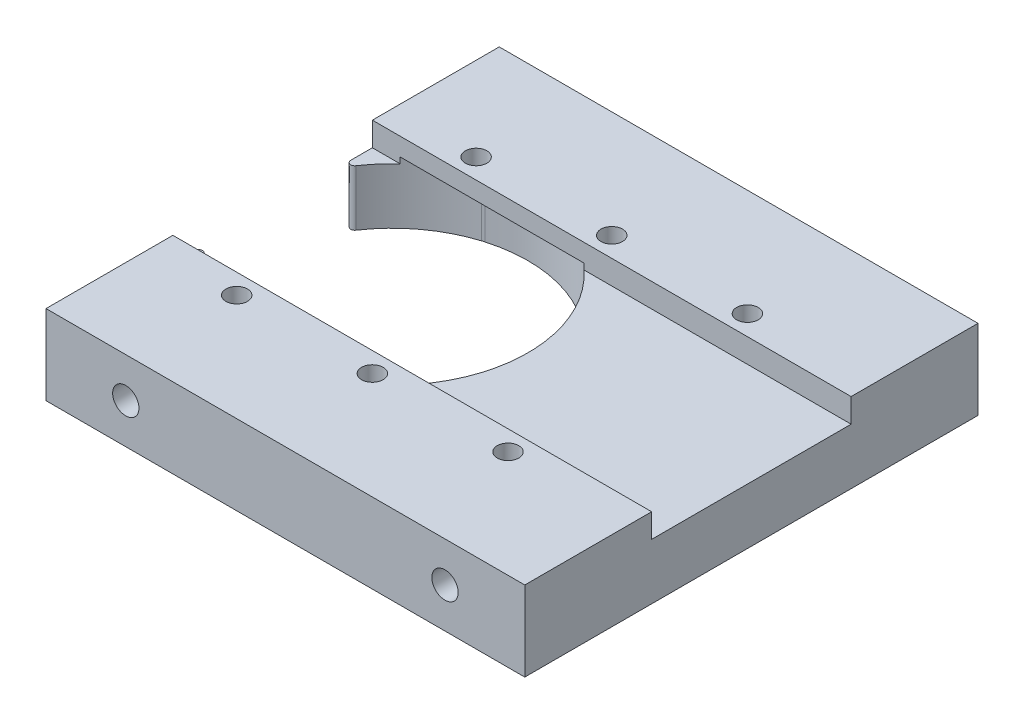
SolidWorks part; units mm, degrees
ref_plane "前视基准面" through (0, 0, 0) normal (0, 0, 1) x (1, 0, 0)
ref_plane "上视基准面" through (0, 0, 0) normal (0, 1, 0) x (1, 0, 0)
ref_plane "右视基准面" through (0, 0, 0) normal (1, 0, 0) x (0, 0, -1)
sketch "草图1" plane through (0, 0, 0) normal (0, 1, 0) x (1, 0, 0)
  line L0 (-36.073, 22.4211) -> (-36.073, 3.819)
  line L1 (-36.073, 22.4211) -> (-25.573, 22.4211)
  line L2 (-25.573, 22.4211) -> (-8.573, 22.4211)
  line L3 (-8.573, 22.4211) -> (8.427, 22.4211)
  line L4 (8.427, 22.4211) -> (23.927, 22.4211)
  line L7 (-8.573, 9.0211) -> (8.427, 9.0211)
  line L8 (23.927, 22.4211) -> (23.927, 9.0211)
  line L9 (23.927, 9.0211) -> (23.927, 6.5211)
  line L10 (23.927, 6.5211) -> (-9.5513, 6.5211)
  line L11 (23.927, 6.5211) -> (23.927, -18.4789)
  line L12 (23.927, -18.4789) -> (-9.5513, -18.4789)
  line L13 (23.927, -18.4789) -> (23.927, -20.9789)
  line L14 (23.927, -20.9789) -> (8.427, -20.9789)
  line L15 (8.427, -20.9789) -> (-8.573, -20.9789)
  line L16 (-8.573, -20.9789) -> (-13.073, -20.9789)
  line L17 (23.927, -20.9789) -> (23.927, -34.3789)
  line L18 (23.927, -34.3789) -> (-36.073, -34.3789)
  line L19 (-36.073, -5.9789) -> (-21.073, -5.9789)
  line L20 (-36.073, -15.7769) -> (-36.073, -34.3789)
  line L23 (-13.073, 9.0211) -> (-8.573, 9.0211)
  circle A0 centre (-25.573, 9.0211) radius 1.35
  circle A1 centre (-8.573, 9.0211) radius 1.35
  circle A2 centre (8.427, 9.0211) radius 1.35
  circle A3 centre (-25.573, -20.9789) radius 1.35
  circle A4 centre (-8.573, -20.9789) radius 1.35
  circle A5 centre (8.427, -20.9789) radius 1.35
  arc A6 (-35.1587, -15.497) -> (-35.1587, 3.5391) centre (-21.073, -5.9789) ccw
  arc A7 (-35.1587, -15.497) -> (-36.073, -15.7769) centre (-35.573, -15.7769) ccw
  arc A8 (-36.073, 3.819) -> (-35.1587, 3.5391) centre (-35.573, 3.819) ccw
  dimension "D13" = 0.5
  dimension "D14" = 0.5
  dimension "D1" = 56.8
  dimension "D2" = 10.5
  dimension "D3" = 17
  dimension "D4" = 17
  dimension "D5" = 15.5
  dimension "D6" = 13.4
  dimension "D7" = 13.4
  dimension "D8" = 2.5
  dimension "D9" = 25
  dimension "D10" = 2.5
  dimension "D11" = 15.5
  dimension "D12" = 15
extrude "凸台-拉伸3" add sketch "草图1" along normal blind 7 contours A6 L12 L11 L10 | L0 A8 A6 A0 A1 A2 L10 L9 L8 L4 L3 L2 L1 | A6 A7 L20 L18 L17 L14 A5 L15 A4 L16 A3 | A6 L16 A4 L15 A5 L14 L13 L12 | A1 | A2 | A4 | A5 region at (-5.1438, 0, -14.9726) region at (9.0402, 0, 5.9789) region at (6.8225, 0, 19.7038) region at (-6.3765, 0, 27.675)
sketch "草图5" plane through (0, 7, 0) normal (0, 1, 0) x (1, 0, 0)
  line L0 (23.927, -34.3789) -> (23.927, -18.4789)
  line L1 (23.927, 22.4211) -> (23.927, -34.3789) construction
  line L2 (23.927, 22.4211) -> (23.927, 6.5211)
  line L3 (-36.073, -18.4789) -> (-36.073, -5.9789)
  line L4 (23.927, -18.4789) -> (-9.5513, -18.4789)
  line L5 (23.927, -18.4789) -> (23.927, -34.3789)
  line L6 (23.927, -34.3789) -> (-36.073, -34.3789)
  line L7 (-36.073, -18.4789) -> (-36.073, -34.3789)
  line L8 (23.927, 6.5211) -> (-9.5513, 6.5211)
  line L9 (23.927, 6.5211) -> (23.927, 22.4211)
  line L10 (23.927, 22.4211) -> (-36.073, 22.4211)
  line L11 (-36.073, 6.5211) -> (-36.073, 22.4211)
  line L12 (-36.073, -5.9789) -> (-21.073, -5.9789)
  line L13 (-32.5947, -18.4789) -> (-36.073, -18.4789)
  line L14 (-32.5947, 6.5211) -> (-36.073, 6.5211)
  arc A0 (-32.5947, -18.4789) -> (-32.5947, 6.5211) centre (-21.073, -5.9789) ccw
  arc M5 (-25.7903, 10.3535) -> (-25.7903, -22.3113) centre (-21.073, -5.9789) cw
  arc M6 (-25.7903, -22.3113) -> (-26.125, -22.2109) centre (-25.573, -20.9789) cw
  arc M7 (-26.125, -22.2109) -> (-35.1587, -15.497) centre (-21.073, -5.9789) cw
  line M9 (-36.073, -15.7769) -> (-36.073, -34.3789)
  line M10 (-36.073, -34.3789) -> (23.927, -34.3789)
  line M11 (23.927, -34.3789) -> (23.927, 22.4211)
  line M12 (23.927, 22.4211) -> (-36.073, 22.4211)
  line M13 (-36.073, 22.4211) -> (-36.073, 3.819)
  arc M15 (-35.1587, 3.5391) -> (-26.125, 10.253) centre (-21.073, -5.9789) cw
  arc M16 (-26.125, 10.253) -> (-25.7903, 10.3535) centre (-25.573, 9.0211) cw
  dimension "D1" = 15.9
  dimension "D2" = 15.9
  dimension "D3" = 12.5
  dimension "D4" = 15
extrude "凸台-拉伸4" add sketch "草图5" along normal blind 0.75 contours L13 L4 M7 M9 M10 M11 M5 M6 region at (-4.8632, 7, 26.9232)
extrude "凸台-拉伸5" add sketch "草图5<3>" along normal blind 0.75 contours L14 L8 M15 M16 M5 M11 M12 M13 region at (-4.8632, 7, -14.9653)
sketch "草图5<3>" plane through (0, 7, 0) normal (0, 1, 0) x (1, 0, 0) same geometry as "草图5"
sketch "草图6" plane through (0, 7.75, 0) normal (0, 1, 0) x (1, 0, 0)
  line L0 (23.927, -34.3789) -> (23.927, -20.9789)
  line L1 (-36.073, -34.3789) -> (23.927, -34.3789)
  line L2 (-36.073, -34.3789) -> (-36.073, -18.4789)
  line L3 (-36.073, -18.4789) -> (23.927, -18.4789)
  line L4 (23.927, -34.3789) -> (23.927, -18.4789)
  line L5 (23.927, -20.9789) -> (8.427, -20.9789)
  line L6 (8.427, -20.9789) -> (-8.573, -20.9789)
  line L7 (-8.573, -20.9789) -> (-25.573, -20.9789)
  circle A0 centre (8.427, -20.9789) radius 1.35
  circle A1 centre (-8.573, -20.9789) radius 1.35
  circle A2 centre (-25.573, -20.9789) radius 1.35
  arc M5 (-26.125, -22.2109) -> (-32.5947, -18.4789) centre (-21.073, -5.9789) cw
  line M6 (-32.5947, -18.4789) -> (-36.073, -18.4789)
  line M7 (-36.073, -18.4789) -> (-36.073, -34.3789)
  line M8 (-36.073, -34.3789) -> (23.927, -34.3789)
  line M9 (23.927, -34.3789) -> (23.927, -18.4789)
  line M10 (23.927, -18.4789) -> (-9.5513, -18.4789)
  arc M11 (-9.5513, -18.4789) -> (-25.7903, -22.3113) centre (-21.073, -5.9789) cw
  arc M12 (-25.7903, -22.3113) -> (-26.125, -22.2109) centre (-25.573, -20.9789) cw
  dimension "D1" = 13.4
  dimension "D2" = 15.5
  dimension "D3" = 17
  dimension "D4" = 17
extrude "凸台-拉伸6" add sketch "草图6" along normal blind 2.25 contours A1 L7 L5 A0 L6 M11 M12 M5 M6 M7 M8 M9 | A2 L7 M11 | A2 L7 L3 M11 M5 | A1 L6 A0 L5 L7 M9 M10 M11 region at (-6.1462, 7.75, 27.7591) region at (6.8225, 7.75, 19.7038) region at (-20.9754, 7.75, 19.6564) region at (-19.8668, 7.75, 21.8507)
sketch "草图7" plane through (0, 7.75, 0) normal (0, 1, 0) x (1, 0, 0)
  line L0 (23.927, 22.4211) -> (23.927, 9.0211)
  line L1 (-36.073, 6.5211) -> (23.927, 6.5211)
  line L2 (-36.073, 6.5211) -> (-36.073, 22.4211)
  line L3 (-36.073, 22.4211) -> (23.927, 22.4211)
  line L4 (23.927, 6.5211) -> (23.927, 22.4211)
  line L5 (23.927, 9.0211) -> (8.427, 9.0211)
  line L6 (8.427, 9.0211) -> (-8.573, 9.0211)
  line L7 (-8.573, 9.0211) -> (-25.573, 9.0211)
  circle A0 centre (8.427, 9.0211) radius 1.35
  circle A1 centre (-8.573, 9.0211) radius 1.35
  circle A2 centre (-25.573, 9.0211) radius 1.35
  line M5 (-36.073, 6.5211) -> (-32.5947, 6.5211)
  arc M6 (-32.5947, 6.5211) -> (-26.125, 10.253) centre (-21.073, -5.9789) cw
  arc M7 (-26.125, 10.253) -> (-25.7903, 10.3535) centre (-25.573, 9.0211) cw
  arc M8 (-25.7903, 10.3535) -> (-9.5513, 6.5211) centre (-21.073, -5.9789) cw
  line M9 (-9.5513, 6.5211) -> (23.927, 6.5211)
  line M10 (23.927, 6.5211) -> (23.927, 22.4211)
  line M11 (23.927, 22.4211) -> (-36.073, 22.4211)
  line M12 (-36.073, 22.4211) -> (-36.073, 6.5211)
  dimension "D1" = 13.4
  dimension "D2" = 15.5
  dimension "D3" = 17
  dimension "D4" = 17
extrude "凸台-拉伸7" add sketch "草图7" along normal blind 2.25 contours A1 L6 A0 L5 L7 M10 M11 M12 M5 M6 M7 M8 | A2 L1 L7 M6 M8 | A2 L7 M8 | A1 L7 L5 A0 L6 M8 M9 M10 region at (-6.1462, 7.75, -15.8012) region at (6.8225, 7.75, -7.7459) region at (-20.9754, 7.75, -7.6985) region at (-19.8668, 7.75, -9.8928)
sketch "草图8" plane through (0, 0, 34.3789) normal (0, 0, 1) x (1, 0, 0)
  line L0 (-36.073, 0) -> (-36.073, 5)
  line L1 (-36.073, 10) -> (-36.073, 0) construction
  line L2 (-36.073, 5) -> (-26.073, 5)
  line L3 (-26.073, 5) -> (13.927, 5)
  circle A0 centre (-26.073, 5) radius 1.65
  circle A1 centre (13.927, 5) radius 1.65
  dimension "D1" = 10
  dimension "D2" = 40
extrude "切除-拉伸1" cut sketch "草图8" against normal blind 5 contours A0 | A1
sketch "草图9" plane through (0, 0, -22.4211) normal (0, 0, -1) x (-1, 0, 0)
  line L0 (36.073, 10) -> (36.073, 5)
  line L1 (36.073, 10) -> (36.073, 0) construction
  line L2 (36.073, 5) -> (26.073, 5)
  line L3 (26.073, 5) -> (-13.927, 5)
  circle A0 centre (26.073, 5) radius 1.65
  circle A1 centre (-13.927, 5) radius 1.65
  dimension "D1" = 10
  dimension "D2" = 40
extrude "切除-拉伸2" cut sketch "草图9" against normal blind 5 contours A0 | A1
